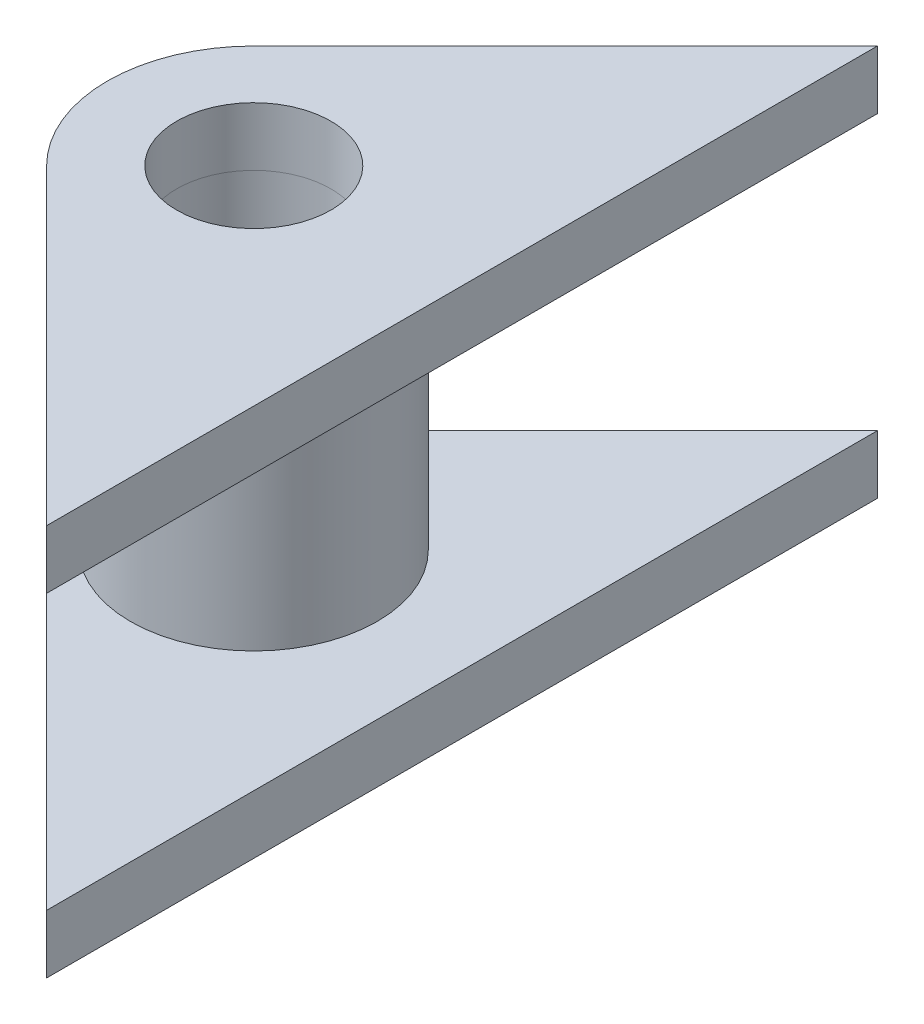
SolidWorks part; units mm, degrees
ref_plane "Front Plane" through (0, 0, 0) normal (0, 0, 1) x (1, 0, 0)
ref_plane "Top Plane" through (0, 0, 0) normal (0, 1, 0) x (1, 0, 0)
ref_plane "Right Plane" through (0, 0, 0) normal (1, 0, 0) x (0, 0, -1)
sketch "Sketch1" plane through (0, 0, 0) normal (0, 1, 0) x (1, 0, 0)
  line L0 (13.5, 26.935) -> (13.5, -26.935)
  line L1 (0, 0) -> (13.5, 0) construction
  line L2 (-6.7175, 6.7175) -> (13.5, 26.935)
  line L3 (-6.7175, -6.7175) -> (13.5, -26.935)
  line L4 (8.5, 0) -> (8.5, -10.9016) construction
  circle A0 centre (0, 0) radius 5
  arc A1 (-6.7175, 6.7175) -> (-6.7175, -6.7175) centre (0, 0) ccw
  circle A2 centre (0, 0) radius 8.5 construction
  dimension "D1" = 10
  dimension "D3" = 9.5
  dimension "D4" = 17
  dimension "D2" = 90
  dimension "D5" = 5
extrude "Boss-Extrude1" add sketch "Sketch1" against normal blind 3.8 from offset 12.7
extrude "Boss-Extrude2" add sketch "Sketch1<2>" along normal blind 3.8 from offset 12.7 separate body offset against normal yes
sketch "Sketch1<2>" plane through (0, 0, 0) normal (0, 1, 0) x (1, 0, 0) same geometry as "Sketch1"
sketch "Sketch3" plane through (0, 0, 0) normal (0, 0, 1) x (1, 0, 0)
  line L0 (0, 0) -> (22.5598, 0) construction
  circle A0 centre (22.5598, 0) radius 12.7
  dimension "D1" = 25.4
sketch "Sketch4" plane through (0, 0, 0) normal (0, 1, 0) x (1, 0, 0)
  circle A0 centre (0, 0) radius 5
  circle A1 centre (0, 0) radius 8
  dimension "D1" = 10
  dimension "D2" = 3
extrude "Boss-Extrude3" add sketch "Sketch4" along normal up to surface (8.9 mm away) and the other way up to surface (8.9 mm away) separate body up to face at (0, 8.9, 5) other way up to face at (2.6956, -8.9, 0)
sketch "Sketch5" plane through (0, 0, 0) normal (0, 1, 0) x (1, 0, 0)
  line L0 (22.5598, 18.9568) -> (22.5598, -18.9568) construction
sketch "Sketch6" plane through (0, 0, 0) normal (0, 0, 1) x (1, 0, 0)
  line L0 (0, 12.7) -> (0, -12.7) construction
  line L1 (5, 12.7) -> (-5, 12.7) construction
delete or keep bodies "Body-Delete1" [suppressed] type delete bodies bodies 103 102
delete or keep bodies "Body-Delete2" [suppressed] type delete bodies bodies 101 102
